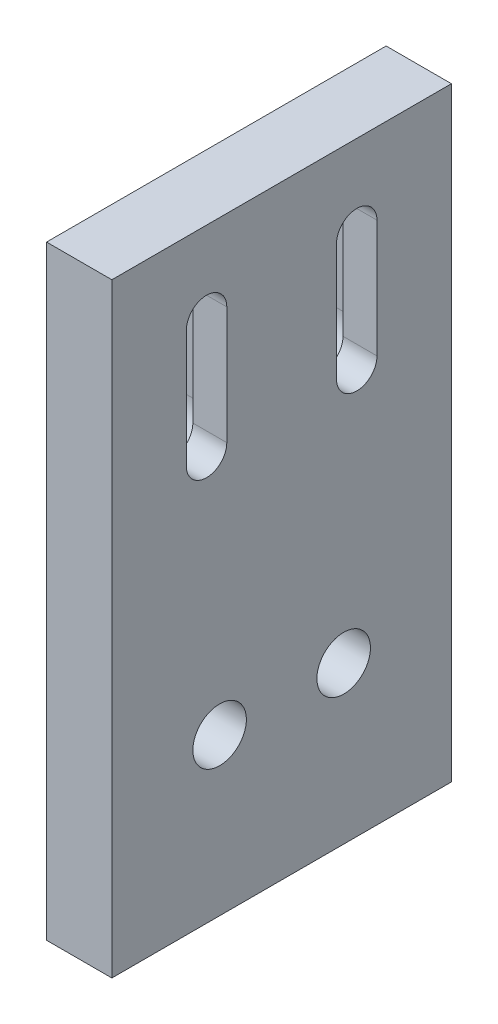
SolidWorks part; units mm, degrees
ref_plane "Front Plane" through (0, 0, 0) normal (0, 0, 1) x (1, 0, 0)
ref_plane "Top Plane" through (0, 0, 0) normal (0, 1, 0) x (1, 0, 0)
ref_plane "Right Plane" through (0, 0, 0) normal (1, 0, 0) x (0, 0, -1)
sketch "ProfileSketch1" plane through (0, 0, 0) normal (0, 0, 1) x (1, 0, 0)
  line L0 (0, 0) -> (5, 0)
  line L1 (5, 0) -> (5, 46.3)
  line L2 (5, 46.3) -> (0, 46.3)
  line L3 (0, 46.3) -> (0, 0)
  dimension "D1" = 46.3
  dimension "D4" = 5
extrude "Boss-Extrude1" add sketch "ProfileSketch1" along normal blind 26
sketch "ProbeSlidingMountSketch4" plane through (0, 0, 0) normal (-1, 0, 0) x (0, 0, 1)
  line L1 (26, 46.3) -> (0, 46.3) construction
  line L3 (5.7, 40.1) -> (5.7, 31.1)
  line L4 (8.8, 40.1) -> (8.8, 31.1)
  line L5 (17.2, 40.1) -> (17.2, 31.1)
  line L6 (20.3, 40.1) -> (20.3, 31.1)
  line L7 (0, 46.3) -> (0, 0) construction
  line L8 (26, 0) -> (0, 0) construction
  line L9 (26, 46.3) -> (26, 0) construction
  arc A0 (8.8, 40.1) -> (5.7, 40.1) centre (7.25, 40.1) ccw
  arc A1 (5.7, 31.1) -> (8.8, 31.1) centre (7.25, 31.1) ccw
  arc A2 (20.3, 40.1) -> (17.2, 40.1) centre (18.75, 40.1) ccw
  arc A3 (17.2, 31.1) -> (20.3, 31.1) centre (18.75, 31.1) ccw
  circle A4 centre (8.25, 12) radius 2.05
  circle A5 centre (17.75, 12) radius 2.05
  dimension "D1" = 3.1
  dimension "D6" = 4.1
  dimension "D2" = 9
  dimension "D7" = 19.1
  dimension "D4" = 11.5
  dimension "D5" = 7.25
  dimension "D9" = 7.25
  dimension "D10" = 12
  dimension "D11" = 9.5
  dimension "D12" = 8.25
  dimension "D13" = 8.25
  dimension "D3" = 6.2
extrude "ProbeSlidingMountCut-Extrude3" cut sketch "ProbeSlidingMountSketch4" against normal through all
sketch "ProbeSlidingMountChannelSketch5" plane through (0, 0, 0) normal (-1, 0, 0) x (0, 0, 1)
  line L0 (7.25, 40.1) -> (7.25, 31.1) construction
  line L1 (10.45, 40.1) -> (10.45, 31.1)
  line L2 (4.05, 40.1) -> (4.05, 31.1)
  line L3 (18.75, 40.1) -> (18.75, 31.1) construction
  line L4 (21.95, 40.1) -> (21.95, 31.1)
  line L5 (15.55, 40.1) -> (15.55, 31.1)
  arc A0 (10.45, 40.1) -> (4.05, 40.1) centre (7.25, 40.1) ccw
  arc A1 (4.05, 31.1) -> (10.45, 31.1) centre (7.25, 31.1) ccw
  arc A2 (21.95, 40.1) -> (15.55, 40.1) centre (18.75, 40.1) ccw
  arc A3 (15.55, 31.1) -> (21.95, 31.1) centre (18.75, 31.1) ccw
  point P4 (7.25, 35.6)
  point P9 (18.75, 35.6)
  dimension "D1" = 6.4
extrude "ProbeSlidingMountChanelCut-Extrude4" cut sketch "ProbeSlidingMountChannelSketch5" against normal blind 2.4
equation "\"ProbeMountHeight\"= + \"ProbeMountUpperHeight\" + \"ProbeMountingHoleSlotLength\" + \"ProbeMountMiddleHeight\" + \"ProbeMountLowerHeight\""
equation "\"D1@ProfileSketch1\"=\"ProbeMountHeight\" "
equation "\"D1@Boss-Extrude1\"= \"ProbeBodyWidth\""
equation "\"ProbeBodyWidth\"= \"InductiveProbeWidth\" + 8.3mm"
equation "\"ProbeMountUpperHeight\"= \"M3ScrewDiameter\" * 2"
equation "\"D4@ProfileSketch1\"=\"ProbeMountDepth\""
equation "\"M3ScrewButtonHeadHeight\"= 2.4mm"
equation "\"D1@ProbeSlidingMountSketch4\" = \"M3ScrewDiameter\""
equation "\"D2@ProbeSlidingMountSketch4\"=\"ProbeMountingHoleSlotLength\""
equation "\"M3ScrewDiameter\"= 3.1mm"
equation "\"ProbeMountDepth\"= \"M3HeatInsertHoleDepth\" + 1mm"
equation "\"M3ScrewButtonHeadDiameter\"= 5.9mm"
equation "\"D1@ProbeSlidingMountChannelSketch5\"=\"M3ScrewButtonHeadDiameter\"+ .5mm"
equation "\"D7@ProbeSlidingMountSketch4\"=\"ProbeMountMiddleHeight\""
equation "\"InductiveProbeWidth\"= 17.7mm"
equation "\"D5@ProbeSlidingMountSketch4\"=(\"ProbeBodyWidth\" - \"ProbeDistanceBetweenMountingHoles\")/2"
equation "\"ProbeDistanceBetweenMountingHoles\"= 11.5mm"
equation "\"D4@ProbeSlidingMountSketch4\"=\"ProbeDistanceBetweenMountingHoles\""
equation "\"M3HeatInsertHoleDepth\"= 4mm"
equation "\"InductiveProbeDistanceBetweenItsMountingHoles\"= 9.5mm"
equation "\"D12@ProbeSlidingMountSketch4\"=(\"ProbeBodyWidth\" - \"InductiveProbeDistanceBetweenItsMountingHoles\")/2"
equation "\"D11@ProbeSlidingMountSketch4\"=\"InductiveProbeDistanceBetweenItsMountingHoles\""
equation "\"M3HeatInsertHoleDiameter\"= 4mm + .1mm'Add .1mm for printing"
equation "\"ProbeMountingHoleSlotLength\"= 9mm"
equation "\"D3@ProbeSlidingMountSketch4\"=\"M3ScrewDiameter\" * 2"
equation "\"InductiveProbeTopHeight\"= 12mm"
equation "\"ProbeMountMiddleHeight\"= \"InductiveProbeTopHeight\" + \"M3ScrewDiameter\" * 2 + .9mm"
equation "\"ProbeMountLowerHeight\"= \"InductiveProbeTopHeight\""
equation "\"D6@ProbeSlidingMountSketch4\"=\"M3HeatInsertHoleDiameter\""
equation "\"D1@ProbeSlidingMountChanelCut-Extrude4\"=\"M3ScrewButtonHeadHeight\""
